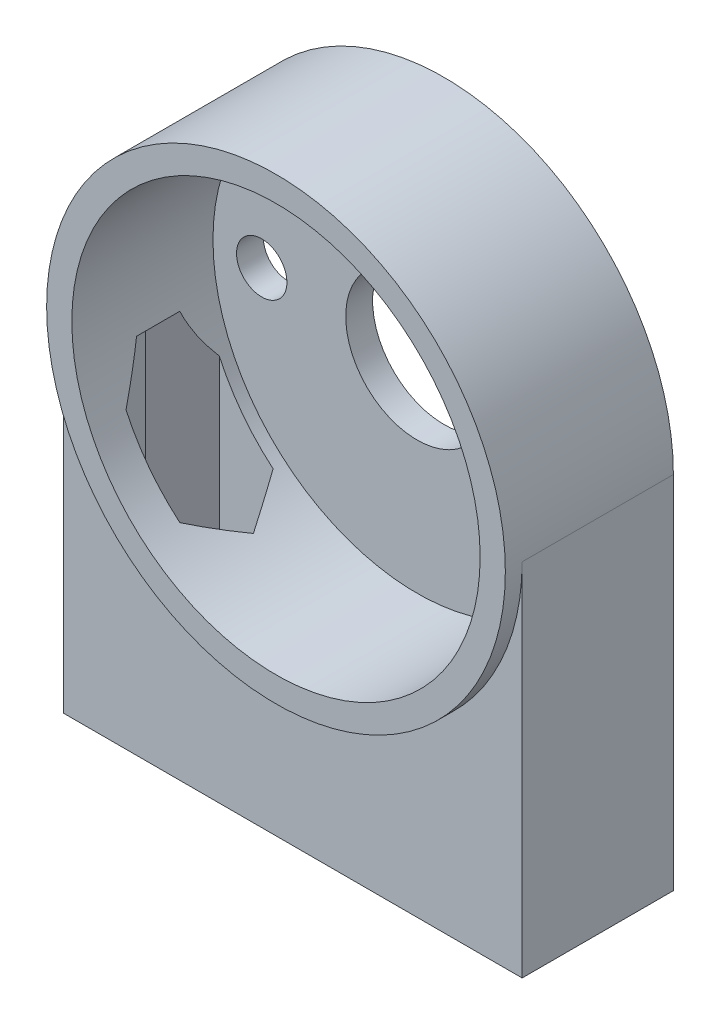
SolidWorks part; units mm, degrees
ref_plane "Front Plane" through (0, 0, 0) normal (0, 0, 1) x (1, 0, 0)
ref_plane "Top Plane" through (0, 0, 0) normal (0, 1, 0) x (1, 0, 0)
ref_plane "Right Plane" through (0, 0, 0) normal (1, 0, 0) x (0, 0, -1)
sketch "Sketch1" plane through (0, 0, 0) normal (0, 0, 1) x (1, 0, 0)
  line L0 (0, -15.015) -> (0, 15.015) construction
  line L1 (15.015, 0) -> (-15.015, 0) construction
  circle A0 centre (0, 21.45) radius 12.15
  circle A1 centre (0, 21.45) radius 13.65
  circle A2 centre (0, 21.45) radius 4.25
  circle A3 centre (9.25, 21.45) radius 1.5
  circle A4 centre (-9.25, 21.45) radius 1.5
  point P12 (0, 0)
  point P13 (0, 0)
  point P14 (0, 0)
  point P15 (0, 0)
  dimension "D1" = 24.3
  dimension "D2" = 27.3
  dimension "D4" = 8.5
  dimension "D5" = 3
  dimension "D3" = 21.45
  dimension "D6" = 9.25
  dimension "D7" = 18.5
extrude "Boss-Extrude1" add sketch "Sketch1" along normal blind 10 contours A1 A0 region at (-13.2639, 21.45, 0)
extrude "Boss-Extrude2" add sketch "Sketch1<4>" along normal blind 1.6 contours A0 A4 A3 A2 region at (-11.8063, 21.45, 0)
sketch "Sketch1<4>" plane through (0, 0, 0) normal (0, 0, 1) x (1, 0, 0) same geometry as "Sketch1"
sketch "Sketch2" plane through (0, 0, 0) normal (0, 0, 1) x (1, 0, 0)
  line L0 (-13.65, 21.45) -> (-13.65, 0)
  line L1 (5.5, 0) -> (-5.5, 0) construction
  line L2 (-13.65, 0) -> (13.65, 0)
  line L3 (13.65, 0) -> (13.65, 21.45)
  circle A0 centre (0, 21.45) radius 13.65 construction
  arc A1 (-13.65, 21.45) -> (13.65, 21.45) centre (0, 21.45) ccw
extrude "Boss-Extrude3" add sketch "Sketch2" along normal blind 9
sketch "Sketch3" plane through (0, 0, 0) normal (0, 1, 0) x (1, 0, 0)
  line L2 (-13.65, -9) -> (-13.65, 0) construction
  line L3 (13.65, -9) -> (13.65, 0) construction
  circle A0 centre (-9.44, -5.1087) radius 1.6
  circle A1 centre (9.44, -5.1087) radius 1.6
  dimension "D1" = 4.21
  dimension "D4" = 3.2
  dimension "D2" = 18.88
  dimension "D3" = 4.21
extrude "Cut-Extrude1" cut sketch "Sketch3" along normal blind 18
sketch "Sketch4" plane through (0, 0, 0) normal (0, 1, 0) x (1, 0, 0)
  line L1 (-7.8379, -2.3337) -> (-11.0421, -2.3337)
  line L2 (-11.0421, -2.3337) -> (-12.6443, -5.1087)
  line L3 (-12.6443, -5.1087) -> (-11.0421, -7.8837)
  line L4 (-11.0421, -7.8837) -> (-7.8379, -7.8837)
  line L5 (-7.8379, -7.8837) -> (-6.2357, -5.1087)
  line L6 (-6.2357, -5.1087) -> (-7.8379, -2.3337)
  line L7 (11.0421, -2.3337) -> (7.8379, -2.3337)
  line L8 (7.8379, -2.3337) -> (6.2357, -5.1087)
  line L9 (6.2357, -5.1087) -> (7.8379, -7.8837)
  line L10 (7.8379, -7.8837) -> (11.0421, -7.8837)
  line L11 (11.0421, -7.8837) -> (12.6443, -5.1087)
  line L12 (12.6443, -5.1087) -> (11.0421, -2.3337)
  circle A0 centre (-9.44, -5.1087) radius 2.775 construction
  circle A1 centre (9.44, -5.1087) radius 2.775 construction
  dimension "D1" = 5.55
  dimension "D2" = 5.55
ref_plane "Plane1" through (0, 3, 0) normal (0, 1, 0) x (1, 0, 0)
extrude "Cut-Extrude2" cut sketch "Sketch4" along normal blind 16 from surface starting at plane "Plane1"
